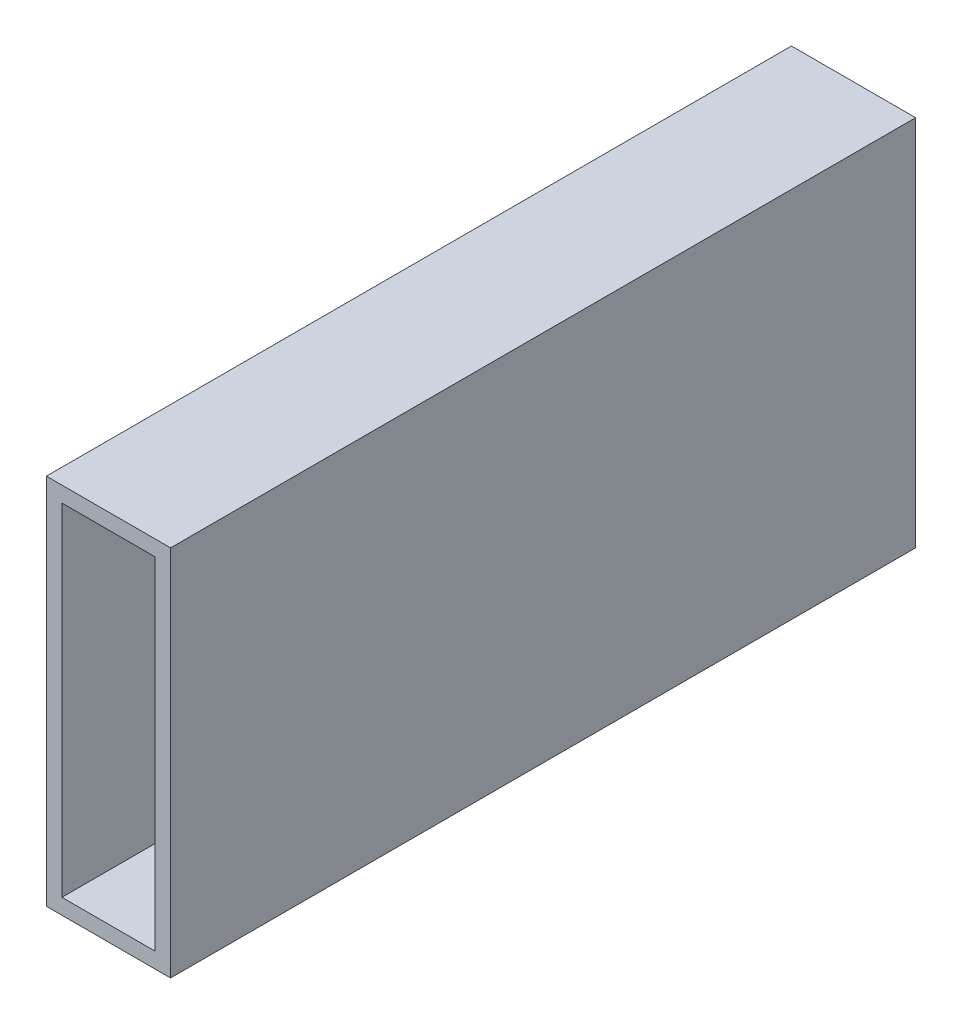
SolidWorks part; units mm, degrees
ref_plane "Front Plane" through (0, 0, 0) normal (0, 0, 1) x (1, 0, 0)
ref_plane "Top Plane" through (0, 0, 0) normal (0, 1, 0) x (1, 0, 0)
ref_plane "Right Plane" through (0, 0, 0) normal (1, 0, 0) x (0, 0, -1)
sketch "Sketch1" plane through (0, 0, 0) normal (0, 0, 1) x (1, 0, 0)
  line L1 (-12.7, -38.1) -> (12.7, -38.1)
  line L2 (-12.7, -38.1) -> (-12.7, 38.1)
  line L3 (-12.7, 38.1) -> (12.7, 38.1)
  line L4 (12.7, -38.1) -> (12.7, 38.1)
  line L5 (-12.7, -38.1) -> (12.7, 38.1) construction
  line L6 (-12.7, 38.1) -> (12.7, -38.1) construction
  point P0 (0, 0)
  dimension "D1" = 25.4
  dimension "D2" = 76.2
extrude "Boss-Extrude1" add sketch "Sketch1" along normal mid plane 152.4
shell "Shell1" thickness 3.175 removed face at (0, 0, -76.2) removed face at (0, 0, 76.2)
